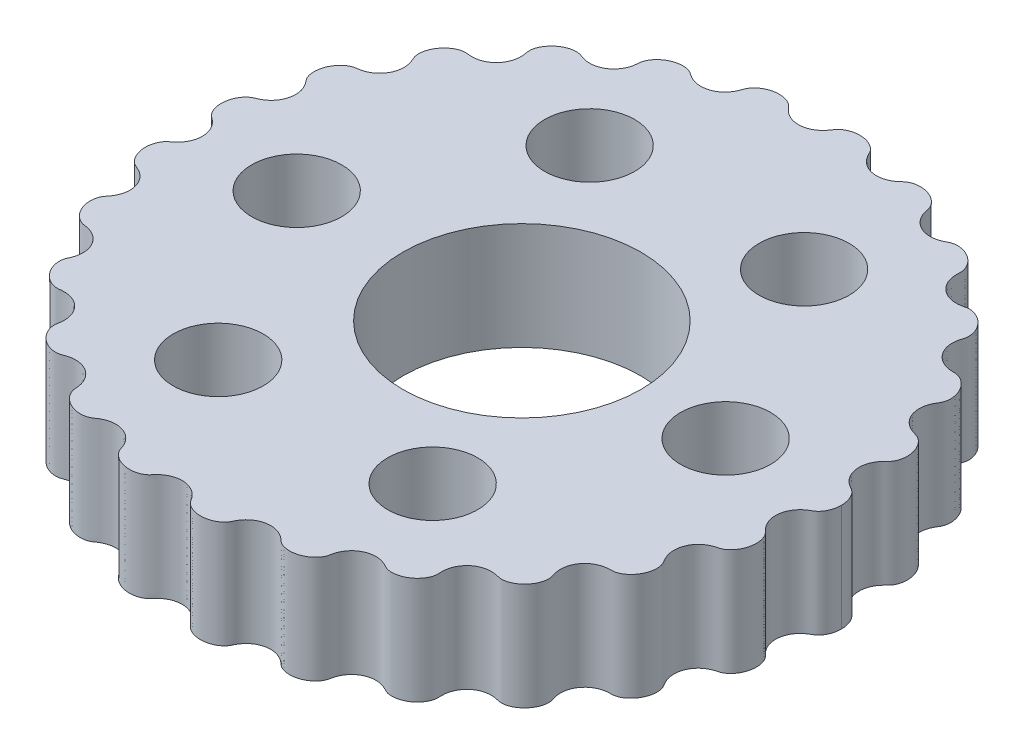
SolidWorks part; units mm, degrees
ref_plane "Front Plane" through (0, 0, 0) normal (0, 0, 1) x (1, 0, 0)
ref_plane "Top Plane" through (0, 0, 0) normal (0, 1, 0) x (1, 0, 0)
ref_plane "Right Plane" through (0, 0, 0) normal (1, 0, 0) x (0, 0, -1)
sketch "Sketch1" plane through (0, 0, 0) normal (0, 1, 0) x (1, 0, 0)
  line L0 (-15.4, 0) -> (14.4, 0) construction
  line L1 (0, 0) -> (0, 14.9128) construction
  line L2 (0, 0) -> (0, -14.9128) construction
  line L3 (0, 0) -> (-0.5, 0) construction
  line L4 (-0.5, 0) -> (-0.5, 15.3103) construction
  line L5 (-0.5, 0) -> (-0.5, -15.3103) construction
  line L6 (14.4, 0) -> (15.5, 0) construction
  line L7 (0, 0) -> (10, 0) construction
  line L8 (7.9, 0) -> (9.5, 0)
  line L9 (-0.5, 0) -> (9.5, 0) construction
  line L10 (-0.5, 15.3103) -> (-0.5, -15.3103) construction
  circle A0 centre (-0.5, 0) radius 16
  circle A1 centre (15.5, 0) radius 1
  circle A2 centre (15.0351, -3.8291) radius 1
  circle A3 centre (13.6673, -7.4356) radius 1
  circle A4 centre (11.4762, -10.61) radius 1
  circle A5 centre (8.589, -13.1677) radius 1
  circle A6 centre (5.1737, -14.9603) radius 1
  circle A7 centre (1.4286, -15.8833) radius 1
  circle A8 centre (-2.4286, -15.8833) radius 1
  circle A9 centre (-6.1737, -14.9603) radius 1
  circle A10 centre (-9.589, -13.1677) radius 1
  circle A11 centre (-12.4762, -10.61) radius 1
  circle A12 centre (-14.6673, -7.4356) radius 1
  circle A13 centre (-16.0351, -3.8291) radius 1
  circle A14 centre (-16.5, 0) radius 1
  circle A15 centre (-16.0351, 3.8291) radius 1
  circle A16 centre (-14.6673, 7.4356) radius 1
  circle A17 centre (-12.4762, 10.61) radius 1
  circle A18 centre (-9.589, 13.1677) radius 1
  circle A19 centre (-6.1737, 14.9603) radius 1
  circle A20 centre (-2.4286, 15.8833) radius 1
  circle A21 centre (1.4286, 15.8833) radius 1
  circle A22 centre (5.1737, 14.9603) radius 1
  circle A23 centre (8.589, 13.1677) radius 1
  circle A24 centre (11.4762, 10.61) radius 1
  circle A25 centre (13.6673, 7.4356) radius 1
  circle A26 centre (15.0351, 3.8291) radius 1
  circle A27 centre (0, 0) radius 10
  circle A28 centre (10, 0) radius 2.1
  circle A29 centre (5, -8.6603) radius 2.1
  circle A30 centre (-5, -8.6603) radius 2.1
  circle A31 centre (-10, 0) radius 2.1
  circle A32 centre (-5, 8.6603) radius 2.1
  circle A33 centre (5, 8.6603) radius 2.1
  circle A34 centre (-6, 8.6603) radius 2.1
  circle A35 centre (4, 8.6603) radius 2.1
  circle A36 centre (9, 0) radius 2.1
  circle A37 centre (4, -8.6603) radius 2.1
  circle A38 centre (-6, -8.6603) radius 2.1
  circle A39 centre (-1, 0) radius 10
  circle A40 centre (-11, 0) radius 2.1
  circle A41 centre (9.5, 0) radius 1.5
  circle A42 centre (4.5, -8.6603) radius 1.5
  circle A43 centre (-5.5, -8.6603) radius 1.5
  circle A44 centre (-10.5, 0) radius 1.5
  circle A45 centre (-5.5, 8.6603) radius 1.5
  circle A46 centre (4.5, 8.6603) radius 1.5
  circle A47 centre (-0.5, 0) radius 5.55
  spline S0 degree 4 number of poles 369 (14.1521, 3.1658) -> (-14.9531, 3.4358) construction
  spline S1 degree 4 number of poles 315 (14.4, 0) -> (-15.4, 0)
  spline S2 degree 4 number of poles 315 (14.4, 0) -> (-15.4, 0)
  spline S3 degree 4 number of poles 315 (-15.4, 0) -> (14.4, 0)
  spline S4 degree 4 number of poles 315 (-15.4, 0) -> (14.4, 0)
  dimension "D1" = 32
  dimension "D2" = 2
  dimension "D4" = 20
  dimension "D5" = 4.2
  dimension "D8" = 6
  dimension "D7" = 10
  dimension "D9" = 10
  dimension "D3" = 26
  dimension "D6" = 6
sketch "Sketch2" plane through (0, 0, 0) normal (0, 1, 0) x (1, 0, 0)
  spline S0 degree 4 number of poles 315 (-15.4, 0) -> (14.4, 0)
  spline S1 degree 4 number of poles 315 (-15.4, 0) -> (14.4, 0)
extrude "Boss-Extrude2" add sketch "Sketch2" against normal blind 5
sketch "Sketch3" plane through (0, 0, 0) normal (0, 1, 0) x (1, 0, 0)
  circle A0 centre (-6, 8.6603) radius 2.1
  circle A1 centre (4, 8.6603) radius 2.1
  circle A2 centre (9, 0) radius 2.1
  circle A3 centre (4, -8.6603) radius 2.1
  circle A4 centre (-6, -8.6603) radius 2.1
  circle A5 centre (-11, 0) radius 2.1
extrude "Cut-Extrude1" cut sketch "Sketch3" against normal through all
sketch "Sketch4" plane through (0, 0, 0) normal (0, 1, 0) x (1, 0, 0)
  circle A0 centre (-0.5, 0) radius 5.55
sketch "Sketch5" plane through (0, 0, 0) normal (0, 1, 0) x (1, 0, 0)
  circle A0 centre (-0.5, 0) radius 5.55
extrude "Cut-Extrude3" cut sketch "Sketch5" against normal through all
